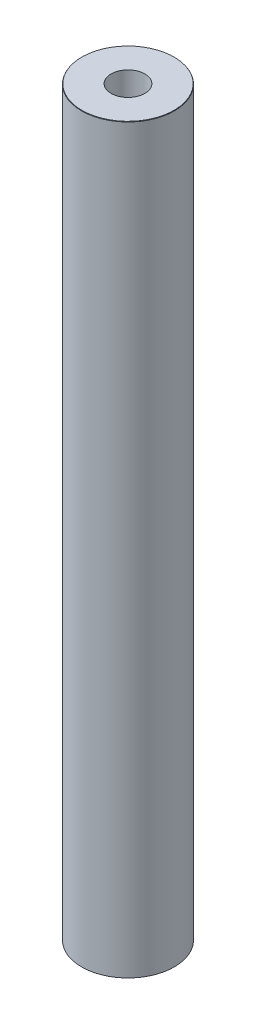
SolidWorks part; units mm, degrees
ref_plane "Front Plane" through (0, 0, 0) normal (0, 0, 1) x (1, 0, 0)
ref_plane "Top Plane" through (0, 0, 0) normal (0, 1, 0) x (1, 0, 0)
ref_plane "Right Plane" through (0, 0, 0) normal (1, 0, 0) x (0, 0, -1)
sketch "Sketch1" plane through (0, 0, 0) normal (0, 1, 0) x (1, 0, 0)
  circle A0 centre (0, 0) radius 37.5
  dimension "SHAFT_OD" = 75
extrude "Boss-Extrude1" add sketch "Sketch1" along normal blind 600
sketch "Sketch2" plane through (0, 0, 0) normal (0, 1, 0) x (1, 0, 0)
  circle A0 centre (0, 0) radius 13.6711
  dimension "BORE_D" = 27.3422
extrude "Cut-Extrude1" cut sketch "Sketch2" along normal through all
chamfer "Chamfer1" distance 0.3392 angle 30 2 edges at (0, 600, 37.5) (0, 0, 37.5) first distance on face at (0, 600, 37.5) first distance on face at (0, 0, 13.6711)
